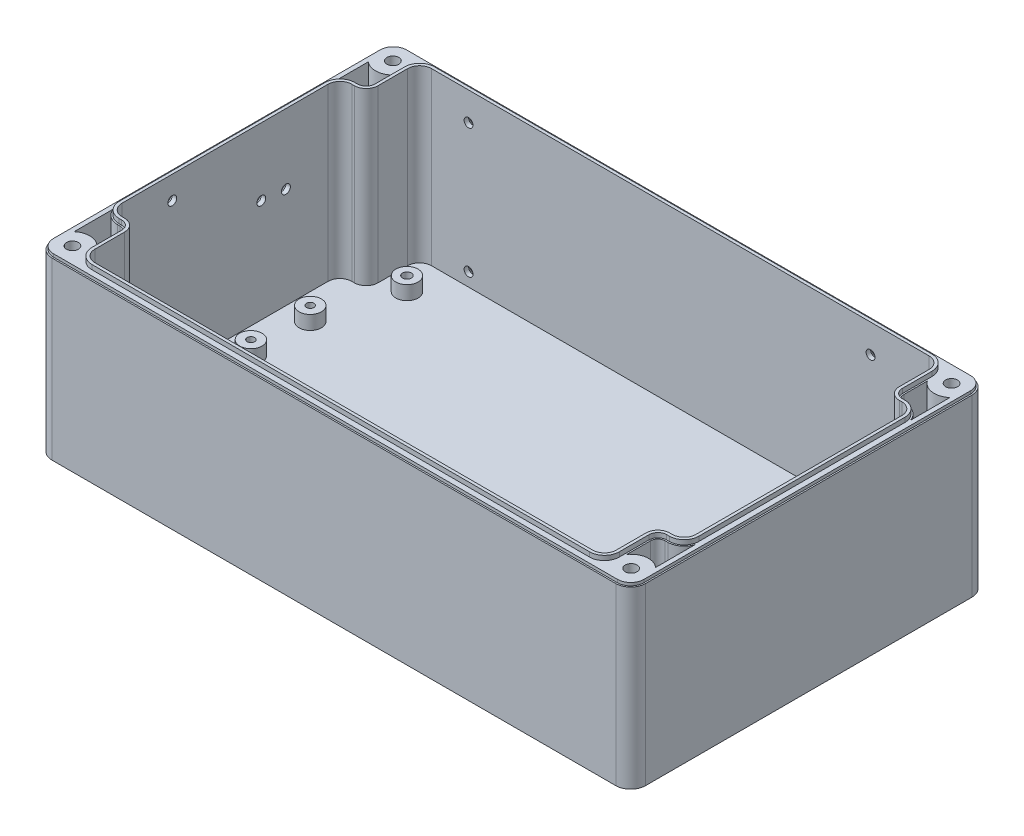
SolidWorks part; units mm, degrees
ref_plane "Front Plane" through (0, 0, 0) normal (0, 0, 1) x (1, 0, 0)
ref_plane "Top Plane" through (0, 0, 0) normal (0, 1, 0) x (1, 0, 0)
ref_plane "Right Plane" through (0, 0, 0) normal (1, 0, 0) x (0, 0, -1)
sketch "Sketch1" plane through (0, 0, 0) normal (0, 1, 0) x (1, 0, 0)
  line L1 (-100, 60) -> (100, 60)
  line L2 (-100, 60) -> (-100, -60)
  line L3 (-100, -60) -> (100, -60)
  line L4 (100, 60) -> (100, -60)
  line L5 (-100, 60) -> (100, -60) construction
  line L6 (-100, -60) -> (100, 60) construction
  point P0 (0, 0)
  dimension "D1" = 200
  dimension "D2" = 120
extrude "Boss-Extrude1" add sketch "Sketch1" along normal blind 60
fillet "Fillet1" radius 5 4 edges at (-100, 30, -60) (100, 30, -60) (100, 30, 60) (-100, 30, 60)
sketch "Sketch2" plane through (0, 60, 0) normal (0, 1, 0) x (1, 0, 0)
  line L0 (0, 60) -> (0, -60) construction
  line L1 (96.7, 56.7) -> (-96.7, 56.7)
  line L2 (96.7, 56.7) -> (96.7, -56.7)
  line L3 (96.7, -56.7) -> (-96.7, -56.7)
  line L4 (-96.7, 56.7) -> (-96.7, -56.7)
  line L5 (96.7, 56.7) -> (-96.7, -56.7) construction
  line L6 (96.7, -56.7) -> (-96.7, 56.7) construction
  line L7 (95, 60) -> (-95, 60) construction
  line L8 (-95, -60) -> (95, -60) construction
  line L9 (-100, 0) -> (99.9439, 0) construction
  line L10 (-100, 55) -> (-100, -55) construction
  line L12 (87.85, -56.7) -> (-87.85, -56.7)
  line L13 (87.85, -56.7) -> (87.85, 56.7)
  line L14 (87.85, 56.7) -> (-87.85, 56.7)
  line L15 (-87.85, -56.7) -> (-87.85, 56.7)
  line L16 (87.85, -56.7) -> (-87.85, 56.7) construction
  line L17 (87.85, 56.7) -> (-87.85, -56.7) construction
  line L18 (96.7, -38.7) -> (-96.7, -38.7)
  line L19 (96.7, -38.7) -> (96.7, 38.7)
  line L20 (96.7, 38.7) -> (-96.7, 38.7)
  line L21 (-96.7, -38.7) -> (-96.7, 38.7)
  line L22 (96.7, -38.7) -> (-96.7, 38.7) construction
  line L23 (96.7, 38.7) -> (-96.7, -38.7) construction
  circle A0 centre (-94.15, 54) radius 2
  circle A2 centre (94.15, 54) radius 2
  circle A3 centre (94.15, -54) radius 2
  circle A4 centre (-94.15, -54) radius 2
  point P0 (0, 0)
  point P18 (0, 0)
  point P19 (0, 0)
  dimension "D5" = 4
  dimension "D1" = 193.4
  dimension "D2" = 113.4
  dimension "D3" = 188.3
  dimension "D4" = 108
  dimension "D6" = 175.7
  dimension "D7" = 77.4
extrude "Cut-Extrude1" cut sketch "Sketch2" against normal offset from surface (56 mm away) 4 contours L20 L13 L1 L15 | L13 L20 L15 L18 | L13 L18 L15 L3 | L15 L20 L4 L18 | L2 L20 L13 L18 | A0 | A4 | A2 | A3 region at (0, 60, -47.7) region at (92.275, 60, 0) region at (0, 60, 0) region at (-92.275, 60, 0) region at (0, 60, 47.7) up to face at (0, 0, 0)
fillet "Fillet2" radius 4 12 edges at (87.85, 32, -56.7) (87.85, 32, -38.7) (96.7, 32, -38.7) (96.7, 32, 38.7) (87.85, 32, 38.7) (87.85, 32, 56.7) (-87.85, 32, 56.7) (-87.85, 32, 38.7) (-96.7, 32, 38.7) (-96.7, 32, -38.7) (-87.85, 32, -56.7) (-87.85, 32, -38.7)
sketch "Sketch3" plane through (0, 60, 0) normal (0, 1, 0) x (1, 0, 0)
  line L1 (83.85, 57.7) -> (-83.85, 57.7)
  line L2 (-88.85, 52.7) -> (-88.85, 42.7)
  line L3 (-91.85, 39.7) -> (-92.7, 39.7)
  line L4 (-97.7, 34.7) -> (-97.7, -34.7)
  line L5 (-92.7, -39.7) -> (-91.85, -39.7)
  line L6 (-88.85, -42.7) -> (-88.85, -52.7)
  line L7 (-83.85, -57.7) -> (83.85, -57.7)
  line L8 (88.85, -52.7) -> (88.85, -42.7)
  line L9 (91.85, -39.7) -> (92.7, -39.7)
  line L10 (97.7, -34.7) -> (97.7, 34.7)
  line L11 (92.7, 39.7) -> (91.85, 39.7)
  line L12 (88.85, 42.7) -> (88.85, 52.7)
  line L13 (87.85, 42.7) -> (87.85, 52.7)
  line L14 (92.7, 38.7) -> (91.85, 38.7)
  line L15 (96.7, -34.7) -> (96.7, 34.7)
  line L16 (91.85, -38.7) -> (92.7, -38.7)
  line L17 (87.85, -52.7) -> (87.85, -42.7)
  line L18 (-83.85, -56.7) -> (83.85, -56.7)
  line L19 (-87.85, -42.7) -> (-87.85, -52.7)
  line L20 (-92.7, -38.7) -> (-91.85, -38.7)
  line L21 (-96.7, 34.7) -> (-96.7, -34.7)
  line L22 (-91.85, 38.7) -> (-92.7, 38.7)
  line L23 (-87.85, 52.7) -> (-87.85, 42.7)
  line L24 (83.85, 56.7) -> (-83.85, 56.7)
  line L25 (87.85, 42.7) -> (87.85, 52.7)
  line L26 (92.7, 38.7) -> (91.85, 38.7)
  line L27 (96.7, -34.7) -> (96.7, 34.7)
  line L28 (91.85, -38.7) -> (92.7, -38.7)
  line L29 (87.85, -52.7) -> (87.85, -42.7)
  line L30 (-83.85, -56.7) -> (83.85, -56.7)
  line L31 (-87.85, -42.7) -> (-87.85, -52.7)
  line L32 (-92.7, -38.7) -> (-91.85, -38.7)
  line L33 (-96.7, 34.7) -> (-96.7, -34.7)
  line L34 (-91.85, 38.7) -> (-92.7, 38.7)
  line L35 (-87.85, 52.7) -> (-87.85, 42.7)
  line L36 (83.85, 56.7) -> (-83.85, 56.7)
  arc A0 (-83.85, 57.7) -> (-88.85, 52.7) centre (-83.85, 52.7) ccw
  arc A1 (-91.85, 39.7) -> (-88.85, 42.7) centre (-91.85, 42.7) ccw
  arc A2 (-92.7, 39.7) -> (-97.7, 34.7) centre (-92.7, 34.7) ccw
  arc A3 (-97.7, -34.7) -> (-92.7, -39.7) centre (-92.7, -34.7) ccw
  arc A4 (-88.85, -42.7) -> (-91.85, -39.7) centre (-91.85, -42.7) ccw
  arc A5 (-88.85, -52.7) -> (-83.85, -57.7) centre (-83.85, -52.7) ccw
  arc A6 (83.85, -57.7) -> (88.85, -52.7) centre (83.85, -52.7) ccw
  arc A7 (91.85, -39.7) -> (88.85, -42.7) centre (91.85, -42.7) ccw
  arc A8 (92.7, -39.7) -> (97.7, -34.7) centre (92.7, -34.7) ccw
  arc A9 (97.7, 34.7) -> (92.7, 39.7) centre (92.7, 34.7) ccw
  arc A10 (88.85, 42.7) -> (91.85, 39.7) centre (91.85, 42.7) ccw
  arc A11 (88.85, 52.7) -> (83.85, 57.7) centre (83.85, 52.7) ccw
  arc A12 (87.85, 42.7) -> (91.85, 38.7) centre (91.85, 42.7) ccw
  arc A13 (96.7, 34.7) -> (92.7, 38.7) centre (92.7, 34.7) ccw
  arc A14 (92.7, -38.7) -> (96.7, -34.7) centre (92.7, -34.7) ccw
  arc A15 (91.85, -38.7) -> (87.85, -42.7) centre (91.85, -42.7) ccw
  arc A16 (83.85, -56.7) -> (87.85, -52.7) centre (83.85, -52.7) ccw
  arc A17 (-87.85, -52.7) -> (-83.85, -56.7) centre (-83.85, -52.7) ccw
  arc A18 (-87.85, -42.7) -> (-91.85, -38.7) centre (-91.85, -42.7) ccw
  arc A19 (-96.7, -34.7) -> (-92.7, -38.7) centre (-92.7, -34.7) ccw
  arc A20 (-92.7, 38.7) -> (-96.7, 34.7) centre (-92.7, 34.7) ccw
  arc A21 (-91.85, 38.7) -> (-87.85, 42.7) centre (-91.85, 42.7) ccw
  arc A22 (-83.85, 56.7) -> (-87.85, 52.7) centre (-83.85, 52.7) ccw
  arc A23 (87.85, 52.7) -> (83.85, 56.7) centre (83.85, 52.7) ccw
  arc A24 (87.85, 42.7) -> (91.85, 38.7) centre (91.85, 42.7) ccw
  arc A25 (96.7, 34.7) -> (92.7, 38.7) centre (92.7, 34.7) ccw
  arc A26 (92.7, -38.7) -> (96.7, -34.7) centre (92.7, -34.7) ccw
  arc A27 (91.85, -38.7) -> (87.85, -42.7) centre (91.85, -42.7) ccw
  arc A28 (83.85, -56.7) -> (87.85, -52.7) centre (83.85, -52.7) ccw
  arc A29 (-87.85, -52.7) -> (-83.85, -56.7) centre (-83.85, -52.7) ccw
  arc A30 (-87.85, -42.7) -> (-91.85, -38.7) centre (-91.85, -42.7) ccw
  arc A31 (-96.7, -34.7) -> (-92.7, -38.7) centre (-92.7, -34.7) ccw
  arc A32 (-92.7, 38.7) -> (-96.7, 34.7) centre (-92.7, 34.7) ccw
  arc A33 (-91.85, 38.7) -> (-87.85, 42.7) centre (-91.85, 42.7) ccw
  arc A34 (-83.85, 56.7) -> (-87.85, 52.7) centre (-83.85, 52.7) ccw
  arc A35 (87.85, 52.7) -> (83.85, 56.7) centre (83.85, 52.7) ccw
  dimension "D1" = 0
  dimension "D2" = 1
extrude "Boss-Extrude2" add sketch "Sketch3" along normal blind 1.55
sketch "Sketch4" plane through (0, 4, 0) normal (0, 1, 0) x (1, 0, 0)
  circle A1 centre (-94.15, 54) radius 2
  circle A2 centre (-94.15, 54) radius 2
  circle A3 centre (94.15, 54) radius 2
  circle A4 centre (94.15, 54) radius 2
  circle A5 centre (-94.15, -54) radius 2
  circle A6 centre (-94.15, -54) radius 2
  circle A7 centre (94.15, -54) radius 2
  circle A8 centre (94.15, -54) radius 2
  dimension "D1" = 0
  dimension "D2" = 0
  dimension "D3" = 0
  dimension "D4" = 0
extrude "Cut-Extrude2" cut sketch "Sketch4" against normal up to next
sketch "Sketch5" plane through (0, 0, 0) normal (0, -1, 0) x (1, 0, 0)
  circle A0 centre (-94.15, 54) radius 3.45
  circle A1 centre (94.15, 54) radius 3.45
  circle A2 centre (94.15, -54) radius 3.45
  circle A3 centre (-94.15, -54) radius 3.45
  dimension "D1" = 6.9
extrude "Cut-Extrude3" cut sketch "Sketch5" against normal blind 52
sketch "Sketch6" plane through (0, 60, 0) normal (0, 1, 0) x (1, 0, 0)
  line L8 (95, 58) -> (-95, 58)
  line L9 (-98, 55) -> (-98, -55)
  line L10 (-95, -58) -> (95, -58)
  line L11 (98, -55) -> (98, 55)
  line L12 (95, 58) -> (-95, 58)
  line L13 (-98, 55) -> (-98, -55)
  line L14 (-95, -58) -> (95, -58)
  line L15 (98, -55) -> (98, 55)
  line L25 (-100, 55) -> (-100, -55) construction
  line L37 (83.85, 58.2) -> (-83.85, 58.2)
  line L38 (89.35, 42.7) -> (89.35, 52.7)
  line L39 (92.7, 40.2) -> (91.85, 40.2)
  line L40 (98.2, -34.7) -> (98.2, 34.7)
  line L41 (91.85, -40.2) -> (92.7, -40.2)
  line L42 (89.35, -52.7) -> (89.35, -42.7)
  line L43 (-83.85, -58.2) -> (83.85, -58.2)
  line L44 (-89.35, -42.7) -> (-89.35, -52.7)
  line L45 (-92.7, -40.2) -> (-91.85, -40.2)
  line L46 (-98.2, 34.7) -> (-98.2, -34.7)
  line L47 (-91.85, 40.2) -> (-92.7, 40.2)
  line L48 (-89.35, 52.7) -> (-89.35, 42.7)
  line L49 (83.85, 58.2) -> (-83.85, 58.2)
  line L50 (89.35, 42.7) -> (89.35, 52.7)
  line L51 (92.7, 40.2) -> (91.85, 40.2)
  line L52 (98.2, -34.7) -> (98.2, 34.7)
  line L53 (91.85, -40.2) -> (92.7, -40.2)
  line L54 (89.35, -52.7) -> (89.35, -42.7)
  line L55 (-83.85, -58.2) -> (83.85, -58.2)
  line L56 (-89.35, -42.7) -> (-89.35, -52.7)
  line L57 (-92.7, -40.2) -> (-91.85, -40.2)
  line L58 (-98.2, 34.7) -> (-98.2, -34.7)
  line L59 (-91.85, 40.2) -> (-92.7, 40.2)
  line L60 (-89.35, 52.7) -> (-89.35, 42.7)
  arc A8 (-95, 58) -> (-98, 55) centre (-95, 55) ccw
  arc A9 (-98, -55) -> (-95, -58) centre (-95, -55) ccw
  arc A10 (95, -58) -> (98, -55) centre (95, -55) ccw
  arc A11 (98, 55) -> (95, 58) centre (95, 55) ccw
  arc A12 (-95, 58) -> (-98, 55) centre (-95, 55) ccw
  arc A13 (-98, -55) -> (-95, -58) centre (-95, -55) ccw
  arc A14 (95, -58) -> (98, -55) centre (95, -55) ccw
  arc A15 (98, 55) -> (95, 58) centre (95, 55) ccw
  circle A24 centre (-94.15, 54) radius 5.85
  circle A25 centre (94.15, 54) radius 5.85
  circle A26 centre (94.15, -54) radius 5.85
  circle A27 centre (-94.15, -54) radius 5.85
  arc A36 (89.35, 52.7) -> (83.85, 58.2) centre (83.85, 52.7) ccw
  arc A37 (89.35, 42.7) -> (91.85, 40.2) centre (91.85, 42.7) ccw
  arc A38 (98.2, 34.7) -> (92.7, 40.2) centre (92.7, 34.7) ccw
  arc A39 (92.7, -40.2) -> (98.2, -34.7) centre (92.7, -34.7) ccw
  arc A40 (91.85, -40.2) -> (89.35, -42.7) centre (91.85, -42.7) ccw
  arc A41 (83.85, -58.2) -> (89.35, -52.7) centre (83.85, -52.7) ccw
  arc A42 (-89.35, -52.7) -> (-83.85, -58.2) centre (-83.85, -52.7) ccw
  arc A43 (-89.35, -42.7) -> (-91.85, -40.2) centre (-91.85, -42.7) ccw
  arc A44 (-98.2, -34.7) -> (-92.7, -40.2) centre (-92.7, -34.7) ccw
  arc A45 (-92.7, 40.2) -> (-98.2, 34.7) centre (-92.7, 34.7) ccw
  arc A46 (-91.85, 40.2) -> (-89.35, 42.7) centre (-91.85, 42.7) ccw
  arc A47 (-83.85, 58.2) -> (-89.35, 52.7) centre (-83.85, 52.7) ccw
  arc A48 (89.35, 52.7) -> (83.85, 58.2) centre (83.85, 52.7) ccw
  arc A49 (89.35, 42.7) -> (91.85, 40.2) centre (91.85, 42.7) ccw
  arc A50 (98.2, 34.7) -> (92.7, 40.2) centre (92.7, 34.7) ccw
  arc A51 (92.7, -40.2) -> (98.2, -34.7) centre (92.7, -34.7) ccw
  arc A52 (91.85, -40.2) -> (89.35, -42.7) centre (91.85, -42.7) ccw
  arc A53 (83.85, -58.2) -> (89.35, -52.7) centre (83.85, -52.7) ccw
  arc A54 (-89.35, -52.7) -> (-83.85, -58.2) centre (-83.85, -52.7) ccw
  arc A55 (-89.35, -42.7) -> (-91.85, -40.2) centre (-91.85, -42.7) ccw
  arc A56 (-98.2, -34.7) -> (-92.7, -40.2) centre (-92.7, -34.7) ccw
  arc A57 (-92.7, 40.2) -> (-98.2, 34.7) centre (-92.7, 34.7) ccw
  arc A58 (-91.85, 40.2) -> (-89.35, 42.7) centre (-91.85, 42.7) ccw
  arc A59 (-83.85, 58.2) -> (-89.35, 52.7) centre (-83.85, 52.7) ccw
  dimension "D1" = 2
  dimension "D2" = 0.5
extrude "Cut-Extrude4" cut sketch "Sketch6" against normal up to surface (56 mm away) contours L59 A58 L60 A24 L13 A57 | A50 L15 A25 L50 A49 L51 | L53 A52 L54 A26 L15 A51 | A56 L13 A27 L56 A55 L57 region at (93.8916, 60, -44.1874) region at (93.8916, 60, 44.1874) region at (-93.8916, 60, -44.1874) region at (-93.8916, 60, 44.1874) up to face at (0, 4, 0)
sketch "Sketch7" plane through (0, 0, 0) normal (0, -1, 0) x (1, 0, 0)
  line L0 (-94.15, 54) -> (-94.15, -54) construction
  line L1 (94.15, -45) -> (-94.15, -45)
  line L2 (94.15, -45) -> (94.15, 45)
  line L3 (94.15, 45) -> (-94.15, 45)
  line L4 (-94.15, -45) -> (-94.15, 45)
  line L5 (94.15, -45) -> (-94.15, 45) construction
  line L6 (94.15, 45) -> (-94.15, -45) construction
  circle A0 centre (-94.15, 45) radius 2.225
  circle A1 centre (94.15, 45) radius 2.225
  circle A2 centre (94.15, -45) radius 2.225
  circle A3 centre (-94.15, -45) radius 2.225
  point P0 (0, 0)
  dimension "D2" = 4.45
  dimension "D1" = 90
extrude "Cut-Extrude5" cut sketch "Sketch7" against normal up to next contours A0 | A1 | A2 | A3
sketch "Sketch8" plane through (0, 4, 0) normal (0, 1, 0) x (1, 0, 0)
  line L0 (0, 60) -> (0, -60) construction
  line L1 (95, 60) -> (-95, 60) construction
  line L2 (-95, -60) -> (95, -60) construction
  line L3 (-100, 0) -> (100, 0) construction
  line L4 (-100, 55) -> (-100, -55) construction
  line L5 (100, -55) -> (100, 55) construction
  line L6 (-80.4, 45) -> (80.4, 45) construction
  line L7 (-80.4, 45) -> (-80.4, -45) construction
  line L8 (-88, 60) -> (-88, -60) construction
  circle A0 centre (-80.4, 45) radius 3.75
  circle A1 centre (-80.4, 45) radius 1.5
  circle A2 centre (80.4, 45) radius 3.75
  circle A3 centre (80.4, 45) radius 1.5
  circle A4 centre (80.4, -45) radius 3.75
  circle A5 centre (80.4, -45) radius 1.5
  circle A6 centre (-80.4, -45) radius 3.75
  circle A7 centre (-80.4, -45) radius 1.5
  circle A8 centre (-57.9, 45) radius 3.75
  circle A9 centre (-57.9, 45) radius 1.25
  circle A12 centre (-57.9, -45) radius 1.25
  circle A13 centre (-57.9, -45) radius 3.75
  circle A16 centre (-88, 0) radius 3.75
  circle A17 centre (-88, 0) radius 1.25
  circle A18 centre (-88, 20) radius 3.75
  circle A19 centre (-88, 20) radius 1.25
  circle A20 centre (-88, -20) radius 1.25
  circle A21 centre (-88, -20) radius 3.75
  circle A22 centre (88, -20) radius 3.75
  circle A23 centre (88, -20) radius 1.25
  circle A24 centre (88, 0) radius 1.25
  circle A25 centre (88, 0) radius 3.75
  circle A26 centre (88, 20) radius 3.75
  circle A27 centre (88, 20) radius 1.25
  dimension "D1" = 7.5
  dimension "D2" = 3
  dimension "D5" = 2.5
  dimension "D3" = 160.8
  dimension "D4" = 90
  dimension "D6" = 22.5
  dimension "D7" = 176
  dimension "D8" = 40
extrude "Boss-Extrude3" add sketch "Sketch8" along normal blind 4.7
sketch "Sketch9" plane through (0, 60, 0) normal (0, 1, 0) x (1, 0, 0)
  line L0 (95, 59.5) -> (-95, 59.5)
  line L1 (-99.5, 55) -> (-99.5, -55)
  line L2 (-95, -59.5) -> (95, -59.5)
  line L3 (99.5, -55) -> (99.5, 55)
  line L4 (95, 60) -> (-95, 60)
  line L5 (-100, 55) -> (-100, -55)
  line L6 (-95, -60) -> (95, -60)
  line L7 (100, -55) -> (100, 55)
  line L8 (95, 60) -> (-95, 60)
  line L9 (-100, 55) -> (-100, -55)
  line L10 (-95, -60) -> (95, -60)
  line L11 (100, -55) -> (100, 55)
  arc A0 (-95, 59.5) -> (-99.5, 55) centre (-95, 55) ccw
  arc A1 (-99.5, -55) -> (-95, -59.5) centre (-95, -55) ccw
  arc A2 (95, -59.5) -> (99.5, -55) centre (95, -55) ccw
  arc A3 (99.5, 55) -> (95, 59.5) centre (95, 55) ccw
  arc A4 (-95, 60) -> (-100, 55) centre (-95, 55) ccw
  arc A5 (-100, -55) -> (-95, -60) centre (-95, -55) ccw
  arc A6 (95, -60) -> (100, -55) centre (95, -55) ccw
  arc A7 (100, 55) -> (95, 60) centre (95, 55) ccw
  arc A8 (-95, 60) -> (-100, 55) centre (-95, 55) ccw
  arc A9 (-100, -55) -> (-95, -60) centre (-95, -55) ccw
  arc A10 (95, -60) -> (100, -55) centre (95, -55) ccw
  arc A11 (100, 55) -> (95, 60) centre (95, 55) ccw
  dimension "D1" = 0
  dimension "D2" = 0.5
extrude "Cut-Extrude6" cut sketch "Sketch9" against normal blind 1
sketch "Sketch10" plane through (0, 8.7, 0) normal (0, 1, 0) x (1, 0, 0)
  circle A1 centre (-57.9, 45) radius 3.75
  circle A2 centre (-57.9, 45) radius 3.75
  dimension "D1" = 0
extrude "Cut-Extrude7" cut sketch "Sketch10" against normal up to surface (4.7 mm away) up to face at (88, 4, -23.75)
sketch "Sketch11" plane through (0, 0, -60) normal (0, 0, -1) x (-1, 0, 0)
  circle A1 centre (71.35, 52) radius 1.5 construction
  circle A2 centre (71.35, 52) radius 1.5
  circle A3 centre (-64.15, 52) radius 1.5 construction
  circle A4 centre (-64.15, 52) radius 1.5
  circle A5 centre (-64.15, 8.5) radius 1.5 construction
  circle A6 centre (-64.15, 8.5) radius 1.5
  circle A7 centre (71.35, 8.5) radius 1.5 construction
  circle A8 centre (71.35, 8.5) radius 1.5
extrude "Cut-Extrude8" cut sketch "Sketch11" against normal up to next
hole_wizard "CSK for M3 Flat Head Machine Screw1" positions "Sketch12" profile "Sketch14" countersink size "M3" standard "ANSI Metric"
sketch "Sketch12" plane through (0, 0, -60) normal (0, 0, -1) x (-1, 0, 0)
  point P0 (71.35, 52)
  point P3 (71.35, 8.5)
  point P6 (-64.15, 8.5)
  point P9 (-64.15, 52)
sketch "Sketch14" plane through (-71.35, 52, -60) normal (1, 0, 0) x (0, 1, 0)
  line L0 (0, 0) -> (0, 4.2003)
  line L1 (0, 4.2003) -> (1.5, 3.299)
  line L2 (1.5, 3.299) -> (1.5, 1.8)
  line L3 (1.5, 1.8) -> (3, 0.3)
  line L4 (3, 0.3) -> (3, 0)
  line L6 (3, 0) -> (0, 0)
  line L7 (-1.5, 1.8) -> (-3, 0.3) construction
  line L10 (0, 4.2003) -> (-1.5, 3.299) construction
  line L11 (0, -6.35) -> (0, 107.95) construction
  dimension "Hole Dia." = 3
  dimension "Hole Depth" = 3.299
  dimension "C'Sink Dia." = 6
  dimension "C'Sink Angle" = 90
  dimension "Drill Angle" = 118
  dimension "Head Clearance" = 0.3
sketch "Sketch15" plane through (-100, 0, 0) normal (-1, 0, 0) x (0, 0, 1)
  circle A0 centre (17.8, 53.8172) radius 1.5 construction
  circle A1 centre (17.8, 53.8172) radius 1.5
  circle A2 centre (-12.2, 38.8172) radius 1.5 construction
  circle A3 centre (-12.2, 38.8172) radius 1.5
  circle A4 centre (20.5, 17.0172) radius 1.8 construction
  circle A5 centre (20.5, 17.0172) radius 1.8
  circle A6 centre (-20.5, 38.0172) radius 1.8 construction
  circle A7 centre (-20.5, 38.0172) radius 1.8
  circle A8 centre (-20.5, 38.0172) radius 1.5
  circle A9 centre (20.5, 17.0172) radius 1.5
extrude "Cut-Extrude9" cut sketch "Sketch15" against normal up to next contours A8 | A3 | A1 | A9 region at (-100, 53.8172, 17.8) region at (-100, 38.8172, -12.2) region at (-100, 38.0172, -20.5) region at (-100, 17.0172, 20.5)
hole_wizard "CSK for M3 Flat Head Machine Screw2" positions "Sketch16" profile "Sketch18" countersink size "M3" standard "ANSI Metric"
sketch "Sketch16" plane through (-100, 0, 0) normal (-1, 0, 0) x (0, 0, 1)
  point P0 (-20.5, 38.0172)
  point P3 (-12.2, 38.8172)
  point P6 (17.8, 53.8172)
  point P9 (20.5, 17.0172)
sketch "Sketch18" plane through (-100, 38.0172, -20.5) normal (0, 1, 0) x (0, 0, 1)
  line L0 (0, 0) -> (0, 4.2003)
  line L1 (0, 4.2003) -> (1.5, 3.299)
  line L2 (1.5, 3.299) -> (1.5, 1.8)
  line L3 (1.5, 1.8) -> (3, 0.3)
  line L4 (3, 0.3) -> (3, 0)
  line L6 (3, 0) -> (0, 0)
  line L7 (-1.5, 1.8) -> (-3, 0.3) construction
  line L10 (0, 4.2003) -> (-1.5, 3.299) construction
  line L11 (0, -6.35) -> (0, 107.95) construction
  dimension "Hole Dia." = 3
  dimension "Hole Depth" = 3.299
  dimension "C'Sink Dia." = 6
  dimension "C'Sink Angle" = 90
  dimension "Drill Angle" = 118
  dimension "Head Clearance" = 0.3
